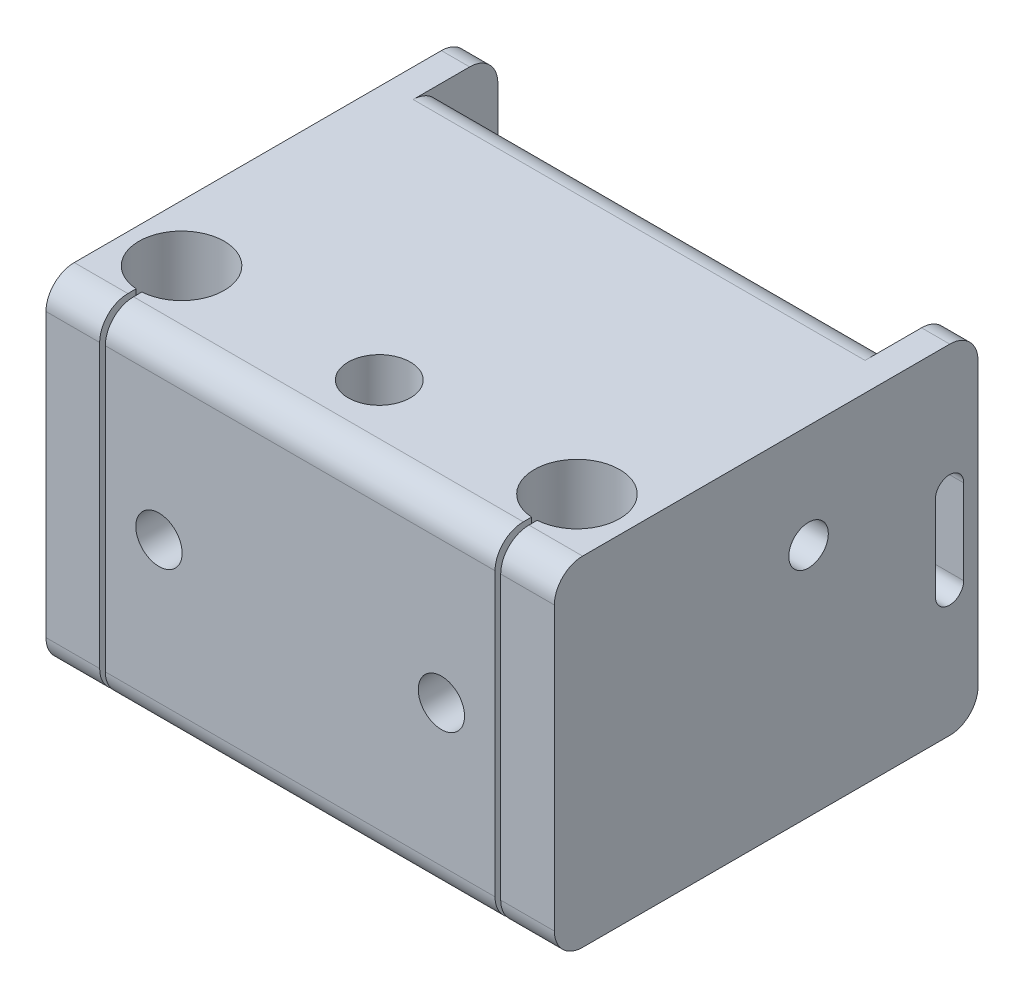
SolidWorks part; units mm, degrees
ref_plane "Front Plane" through (0, 0, 0) normal (0, 0, 1) x (1, 0, 0)
ref_plane "Top Plane" through (0, 0, 0) normal (0, 1, 0) x (1, 0, 0)
ref_plane "Right Plane" through (0, 0, 0) normal (1, 0, 0) x (0, 0, -1)
sketch "Sketch1" plane through (0, 0, 0) normal (1, 0, 0) x (0, 0, -1)
  line L1 (-27.5, -30) -> (27.5, -30)
  line L2 (-32.5, -25) -> (-32.5, 25)
  line L3 (-27.5, 30) -> (27.5, 30)
  line L4 (32.5, -25) -> (32.5, 25)
  line L5 (-32.5, -30) -> (32.5, 30) construction
  line L6 (-32.5, 30) -> (32.5, -30) construction
  arc A0 (-27.5, -30) -> (-32.5, -25) centre (-27.5, -25) cw
  arc A1 (27.5, -30) -> (32.5, -25) centre (27.5, -25) ccw
  arc A2 (27.5, 30) -> (32.5, 25) centre (27.5, 25) cw
  arc A3 (-32.5, 25) -> (-27.5, 30) centre (-27.5, 25) cw
  point P0 (0, 0)
  dimension "D3" = 5
  dimension "D1" = 60
  dimension "D2" = 65
extrude "Boss-Extrude1" add sketch "Sketch1" along normal blind 90
sketch "Sketch2" plane through (0, 30, 0) normal (0, 1, 0) x (1, 0, 0)
  line L0 (0, -18.5) -> (90, -18.5) construction
  line L1 (0, 27.5) -> (0, -27.5) construction
  line L2 (90, 27.5) -> (90, -27.5) construction
  line L3 (90, -32.5) -> (0, -32.5) construction
  circle A0 centre (10, -18.5) radius 7.55
  circle A1 centre (80, -18.5) radius 7.55
  circle A2 centre (45, -18.5) radius 5.5
  point P12 (45, -18.5)
  dimension "D1" = 15.1
  dimension "D2" = 70
  dimension "D5" = 11
  dimension "D3" = 35
  dimension "D4" = 14
extrude "Cut-Extrude1" cut sketch "Sketch2" against normal blind 90
sketch "Sketch3" plane through (0, 0, 32.5) normal (0, 0, 1) x (1, 0, 0)
  line L0 (0, 0) -> (90, 0) construction
  line L1 (0, 25) -> (0, -25) construction
  line L2 (90, 25) -> (90, -25) construction
  circle A0 centre (20, 0) radius 4.1
  circle A1 centre (70, 0) radius 4.1
  point P10 (45, 0)
  dimension "D2" = 8.2
  dimension "D3" = 8.2
  dimension "D1" = 50
  dimension "D4" = 25
extrude "Cut-Extrude2" cut sketch "Sketch3" against normal blind 90
sketch "Sketch4" plane through (0, 0, -32.5) normal (0, 0, -1) x (-1, 0, 0)
  line L0 (-85, 25) -> (-85, -25)
  line L1 (-5, -25) -> (-5, 25)
  line L4 (0, -25) -> (0, 25)
  line L5 (0, 25) -> (-90, 25)
  line L6 (-90, 25) -> (-90, -25)
  line L7 (0, 25) -> (-90, 25)
  line L8 (0, -25) -> (0, 25)
  line L9 (-90, -25) -> (0, -25)
  line L10 (-90, 25) -> (-90, -25)
  line L11 (-90, -25) -> (0, -25)
  circle M5 centre (-70, 0) radius 4.1
  circle M6 centre (-20, 0) radius 4.1
  line M8 (0, 25) -> (-90, 25)
  line M10 (-90, -25) -> (0, -25)
  dimension "D1" = 0
  dimension "D2" = 5
extrude "Cut-Extrude3" cut sketch "Sketch4" against normal blind 42 contours L1 L0 M10 M8 M6 M5 region at (45, 0, -32.5)
sketch "Sketch5" plane through (5, 0, 0) normal (1, 0, 0) x (0, 0, -1)
  line L0 (-9.5, 0) -> (12, 0) construction
  line L1 (12, 0) -> (12, 15.5) construction
  line L2 (12, 15.5) -> (-3.5, 15.5) construction
  line L3 (-9.5, -25) -> (-9.5, 25) construction
  circle A0 centre (12, 0) radius 11.5
  circle A1 centre (-3.5, 15.5) radius 1.75
  circle A2 centre (27.5, 15.5) radius 1.75
  circle A3 centre (27.5, -15.5) radius 1.75
  circle A4 centre (-3.5, -15.5) radius 1.75
  dimension "D2" = 23
  dimension "D4" = 3.5
  dimension "D1" = 21.5
  dimension "D3" = 15.5
  dimension "D5" = 2
  dimension "D6" = 2
extrude "Cut-Extrude4" cut sketch "Sketch5" against normal blind 42
ref_plane "Plane1" through (0, 0, 7.5) normal (0, 0, -1) x (-1, 0, 0)
sketch "Sketch7" plane through (0, 0, 7.5) normal (0, 0, -1) x (-1, 0, 0)
  line L0 (-70, -7) -> (-70, -25)
  line L1 (-63, 0) -> (-63, -25)
  line L2 (-63, 0) -> (-63, 25)
  line L3 (-68, 25) -> (-68, 6.7082)
  line L4 (-85, -25) -> (-5, -25)
  line L5 (-5, -25) -> (-5, 25)
  line L6 (-85, -25) -> (-5, -25)
  line L7 (-85, 25) -> (-85, -25)
  line L8 (-5, 25) -> (-85, 25)
  line L9 (-68, 6.7082) -> (-68, 3.4641)
  line L10 (-5, 25) -> (-85, 25)
  line L11 (-77, 19.3619) -> (-70, 19.3619)
  line L12 (-70, 19.3619) -> (-70, 4)
  line L13 (-77, 19.3619) -> (-77, 0)
  arc A0 (-70, 4) -> (-68, 3.4641) centre (-70, 0) ccw
  arc A1 (-63, 0) -> (-70, -7) centre (-70, 0) ccw
  dimension "D1" = 8
  dimension "D2" = 3
  dimension "D4" = 5
  dimension "D3" = 0
extrude "Boss-Extrude2" add sketch "Sketch7" along normal up to surface (40 mm away) contours L1 A1 L9 A0 L12 L0 L6 | A1 L12 L11 L13 | A1 L2 L10 L3 region at (67.898, -8.9994, 7.5) region at (73.7098, 12.3418, 7.5) region at (65.3961, 14.9102, 7.5) up to face at (87.5, 0, -32.5)
chamfer "Chamfer1" distance 3 angle 45 4 edges at (70, -25, -12.5) (68, 25, -12.5) (63, -25, -12.5) (63, 25, -12.5)
sketch "Sketch8" plane through (70, 0, 0) normal (-1, 0, 0) x (0, 0, 1)
  line L0 (-12.5, 19.3619) -> (-12.5, 4) construction
  line L1 (-32.5, 19.3619) -> (7.5, 19.3619) construction
  line L2 (-32.5, 4) -> (7.5, 4) construction
  circle A0 centre (-12.5, 11.6809) radius 2.25
  dimension "D1" = 4.5
extrude "Cut-Extrude5" cut sketch "Sketch8" against normal blind 42 and the other way blind 23
sketch "Sketch9" plane through (63, 0, 0) normal (-1, 0, 0) x (0, 0, 1)
  line L0 (-12.5, 18.1473) -> (-18.1, 14.9141)
  line L1 (-12.5, 7.524) -> (-8.9, 9.6025)
  line L2 (-8.9, 9.6025) -> (-8.9, 13.7594)
  line L3 (-8.9, 13.7594) -> (-12.5, 15.8379)
  line L4 (-12.5, 15.8379) -> (-16.1, 13.7594)
  line L5 (-16.1, 13.7594) -> (-16.1, 9.6025)
  line L6 (-16.1, 9.6025) -> (-12.5, 7.524)
  line L7 (-18.1, 14.9141) -> (-18.1, 8.4478)
  line L8 (-18.1, 8.4478) -> (-12.5, 5.2146)
  line L9 (-12.5, 5.2146) -> (-6.9, 8.4478)
  line L10 (-6.9, 8.4478) -> (-6.9, 14.9141)
  line L11 (-6.9, 14.9141) -> (-12.5, 18.1473)
  circle A0 centre (-12.5, 11.6809) radius 3.6 construction
  dimension "D1" = 7.2
  dimension "D2" = 2
extrude "Boss-Extrude3" add sketch "Sketch9" along normal blind 3
sketch "Sketch10" plane through (0, 30, 0) normal (0, 1, 0) x (1, 0, 0)
  line L0 (10, -18.5) -> (10, -42.3505)
  line L1 (80, -18.5) -> (80, -42.3505)
extrude "Cut-Extrude-Thin1" cut sketch "Sketch10" against normal blind 70 thin thin type mid plane wall 1
sketch "Sketch11" plane through (0, -30, 0) normal (0, -1, 0) x (-1, 0, 0)
  circle A0 centre (-45, -18.5) radius 11.5
  dimension "D1" = 23
extrude "Cut-Extrude6" cut sketch "Sketch11" against normal blind 7
sketch "Sketch12" plane through (0, -23, 0) normal (0, -1, 0) x (-1, 0, 0)
  line L0 (-45, -18.5) -> (-45, -26.5) construction
  circle A0 centre (-45, -26.5) radius 1.95
  circle A1 centre (-53, -18.5) radius 1.95
  circle A3 centre (-37, -18.5) radius 1.95
  circle A4 centre (-45, -10.5) radius 1.95 [skipped]
  point P13 (-45, -18.5)
  dimension "D1" = 3.9
  dimension "D2" = 8
  dimension "D3" = 4
extrude "Cut-Extrude7" cut sketch "Sketch12" against normal blind 15
chamfer "Chamfer2" distance 2 angle 45 1 edges at (5, 0, -23.5)
sketch "Sketch13" plane through (90, 0, 0) normal (1, 0, 0) x (0, 0, -1)
  circle A0 centre (12.5, 11.6809) radius 3.5
  dimension "D1" = 7
extrude "Cut-Extrude8" cut sketch "Sketch13" against normal blind 8
sketch "Sketch14" plane through (0, 0, 0) normal (-1, 0, 0) x (0, 0, 1)
  line L0 (-27.5, -30) -> (-42.5, -30)
  line L1 (-42.5, -30) -> (-42.5, 30)
  line L2 (-42.5, 30) -> (-27.5, 30)
  line L3 (-32.5, 25) -> (-32.5, -25)
  arc A0 (-27.5, 30) -> (-32.5, 25) centre (-27.5, 25) ccw
  arc A1 (-32.5, -25) -> (-27.5, -30) centre (-27.5, -25) ccw
  dimension "D1" = 10
extrude "Boss-Extrude4" add sketch "Sketch14" against normal up to surface (5 mm away) up to face at (5, 0, 1.5)
sketch "Sketch15" plane through (90, 0, 0) normal (1, 0, 0) x (0, 0, -1)
  line L0 (27.5, -30) -> (42.5, -30)
  line L1 (42.5, -30) -> (42.5, 30)
  line L2 (42.5, 30) -> (27.5, 30)
  line L3 (27.5, 30) -> (27.5, -30)
  line L4 (42.5, -30) -> (42.5, 30) construction
extrude "Boss-Extrude5" add sketch "Sketch15" against normal up to surface (5 mm away) up to face at (85, 11.6809, -16)
fillet "Fillet1" radius 5 4 edges at (87.5, 30, -42.5) (2.5, 30, -42.5) (2.5, -30, -42.5) (87.5, -30, -42.5)
sketch "Sketch16" plane through (90, 0, 0) normal (1, 0, 0) x (0, 0, -1)
  line L0 (37.4615, -7.5) -> (37.4615, 7.5) construction
  line L1 (34.9615, -7.5) -> (34.9615, 7.5)
  line L2 (39.9615, -7.5) -> (39.9615, 7.5)
  line L3 (42.5, -25) -> (42.5, 25) construction
  arc A0 (34.9615, -7.5) -> (39.9615, -7.5) centre (37.4615, -7.5) ccw
  arc A1 (39.9615, 7.5) -> (34.9615, 7.5) centre (37.4615, 7.5) ccw
  point P2 (37.4615, 0)
  point P7 (0, 0)
  point P10 (42.5, 0)
  dimension "D1" = 15
  dimension "D2" = 5
extrude "Cut-Extrude9" cut sketch "Sketch16" against normal blind 10
